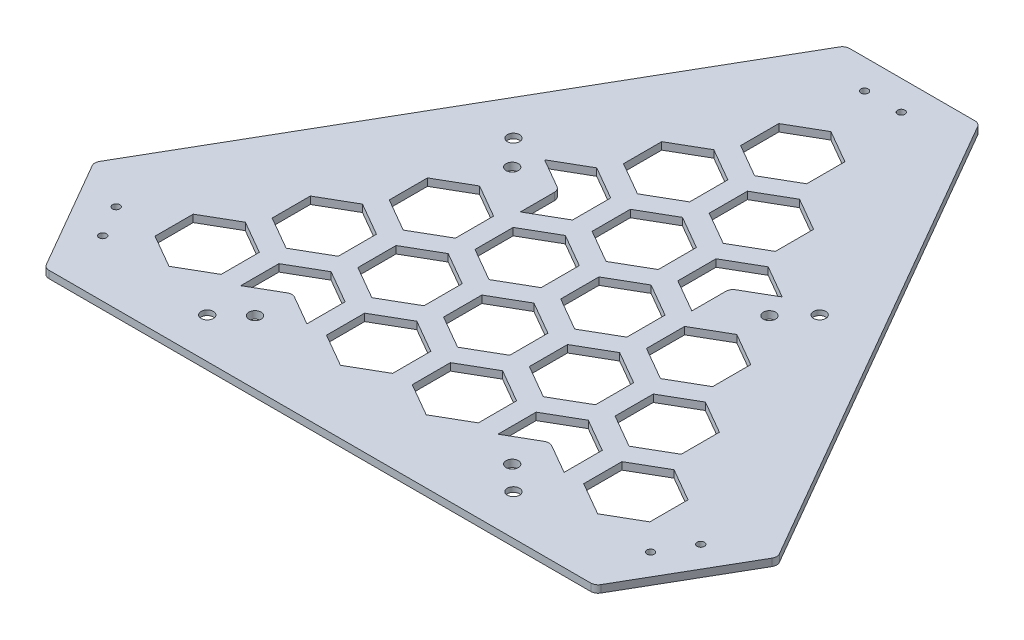
SolidWorks part; units mm, degrees
ref_plane "前基準面" through (0, 0, 0) normal (0, 0, 1) x (1, 0, 0)
ref_plane "上基準面" through (0, 0, 0) normal (0, 1, 0) x (1, 0, 0)
ref_plane "右基準面" through (0, 0, 0) normal (1, 0, 0) x (0, 0, -1)
sketch "草圖1" plane through (0, 0, 0) normal (0, 1, 0) x (1, 0, 0)
  line L0 (0, 0) -> (328.0593, 0) construction
  line L1 (139.6188, -49.0748) -> (27.3094, 145.4508)
  line L2 (-27.3094, 145.4508) -> (-139.6188, -49.0748)
  line L3 (-112.3094, -96.376) -> (112.3094, -96.376)
  line L4 (-27.3094, 145.4508) -> (27.3094, 145.4508)
  line L5 (-139.6188, -49.0748) -> (-112.3094, -96.376)
  line L6 (139.6188, -49.0748) -> (112.3094, -96.376)
  line L7 (-100, -96.376) -> (100, -96.376)
  line L8 (-100, -96.376) -> (-100, -92.376)
  line L9 (-100, -92.376) -> (100, -92.376)
  line L10 (100, -92.376) -> (100, -96.376)
  line L11 (33.4641, 134.7906) -> (133.4641, -38.4145)
  line L12 (133.4641, -38.4145) -> (130, -40.4145)
  line L13 (130, -40.4145) -> (30, 132.7906)
  line L14 (30, 132.7906) -> (33.4641, 134.7906)
  line L15 (-33.4641, 134.7906) -> (-133.4641, -38.4145)
  line L16 (-133.4641, -38.4145) -> (-130, -40.4145)
  line L17 (-130, -40.4145) -> (-30, 132.7906)
  line L18 (-30, 132.7906) -> (-33.4641, 134.7906)
  line L19 (135, -49.0748) -> (130.8333, -56.2917)
  line L20 (130, -40.4145) -> (135, -49.0748)
  line L21 (110, -92.376) -> (100, -92.376)
  line L22 (127.3692, -54.2917) -> (110.7026, -83.1592)
  line L23 (127.3692, -54.2917) -> (130.8333, -56.2917)
  line L24 (110.7026, -83.1592) -> (114.1667, -85.1592)
  line L25 (114.1667, -85.1592) -> (110, -92.376)
  line L26 (-25, 141.4508) -> (-16.6667, 141.4508)
  line L27 (-30, 132.7906) -> (-25, 141.4508)
  line L28 (25, 141.4508) -> (30, 132.7906)
  line L29 (-16.6667, 137.4508) -> (16.6667, 137.4508)
  line L30 (-16.6667, 137.4508) -> (-16.6667, 141.4508)
  line L31 (16.6667, 137.4508) -> (16.6667, 141.4508)
  line L32 (16.6667, 141.4508) -> (25, 141.4508)
  line L33 (-135, -49.0748) -> (-130.8333, -56.2917)
  line L34 (-130, -40.4145) -> (-135, -49.0748)
  line L35 (-100, -92.376) -> (-110, -92.376)
  line L36 (-127.3692, -54.2917) -> (-110.7026, -83.1592)
  line L37 (-127.3692, -54.2917) -> (-130.8333, -56.2917)
  line L38 (-110.7026, -83.1592) -> (-114.1667, -85.1592)
  line L39 (-114.1667, -85.1592) -> (-110, -92.376)
  line L40 (-16.6667, 141.4508) -> (16.6667, 141.4508)
  line L41 (-130.8333, -56.2917) -> (-114.1667, -85.1592)
  line L42 (130.8333, -56.2917) -> (114.1667, -85.1592)
  line L43 (-62.5, -79.876) -> (62.5, -79.876) construction
  line L44 (-62.5, -79.876) -> (-62.5, 45.124) construction
  circle A0 centre (0, 0) radius 96.376 construction
  point P1 (-27.3094, 145.4508)
  point P7 (27.3094, 145.4508)
  point P9 (-139.6188, -49.0748)
  point P10 (139.6188, -49.0748)
  point P11 (112.3094, -96.376)
  point P12 (-112.3094, -96.376)
  point P44 (-62.5, -79.876)
  point P47 (65.57, 71.1815)
  point P48 (119.25, -21.795)
  point P49 (62.5, -79.876)
  point P50 (62.5, 45.124)
  point P51 (-62.5, 45.124)
  point P55 (-78.5, -92.376)
  point P56 (28.86, -92.376)
  point P57 (-40.75, 114.171)
  point P58 (-94.43, 21.1945)
  dimension "D1" = 224.6188
  dimension "D2" = 54.6188
  dimension "D3" = 224.6188
  dimension "D4" = 224.6188
  dimension "D5" = 54.6188
  dimension "D6" = 54.6188
  dimension "D7" = 120
  dimension "D8" = 120
  dimension "D9" = 200
  dimension "D10" = 12.3094
  dimension "D11" = 4
  dimension "D12" = 4
  dimension "D13" = 200
  dimension "D14" = 12.3094
  dimension "D15" = 4
  dimension "D16" = 4
  dimension "D17" = 200
  dimension "D18" = 12.3094
  dimension "D19" = 4
  dimension "D20" = 50
  dimension "D21" = 4
  dimension "D22" = 4
  dimension "D23" = 33.3333
  dimension "D24" = 4
  dimension "D25" = 50
  dimension "D26" = 4
  dimension "D27" = 4
  dimension "D28" = 33.3333
  dimension "D29" = 50
  dimension "D30" = 4
  dimension "D31" = 4
  dimension "D32" = 33.3333
  dimension "D33" = 4
  dimension "D34" = 12.5
  dimension "D35" = 37.5
  dimension "D38" = 125
  dimension "D39" = 125
  dimension "D40" = 31.5
  dimension "D41" = 107.36
  dimension "D42" = 31.5
  dimension "D43" = 107.36
  dimension "D44" = 31.5
  dimension "D45" = 107.36
  dimension "D36" = 2
  dimension "D37" = 2
extrude "填料-伸長1" add sketch "草圖1" against normal blind 3 contours L38 L39 L35 L9 L21 L25 L24 L22 L23 L19 L20 L13 L28 L32 L31 L29 L30 L26 L27 L17 L34 L33 L37 L36 | L17 L18 L2 L16 | L40 L30 L29 L31 | L26 L40 L32 L28 L14 L1 L4 L2 L18 L27 | L14 L13 L12 L1 | L42 L23 L22 L24 | L19 L42 L25 L21 L10 L3 L6 L1 L12 L20 | L10 L9 L8 L3 | L41 L33 L34 L16 L2 L5 L3 L8 L35 L39 | L37 L41 L38 L36 region at (123.0127, 0, 71.0214) region at (81.7321, 0, -47.188) region at (0, 0, -142.0428) region at (0, 0, 0) region at (0, 0, 94.376) region at (-123.0127, 0, 71.0214) region at (120.7679, 0, 69.7254) region at (-81.7321, 0, -47.188) region at (0, 0, -139.4508) region at (-120.7679, 0, 69.7254)
sketch "草圖3" plane through (0, 0, 0) normal (0, 1, 0) x (1, 0, 0)
  circle A0 centre (-62.5, 45.124) radius 2.5
  circle A1 centre (62.5, 45.124) radius 2.5
  circle A2 centre (-62.5, -79.876) radius 2.5
  circle A3 centre (62.5, -79.876) radius 2.5
  dimension "D1" = 5
  dimension "D2" = 5
  dimension "D3" = 5
  dimension "D4" = 5
extrude "除料-伸長1" cut sketch "草圖3" against normal through all
sketch "草圖4" plane through (0, -3, 0) normal (0, -1, 0) x (1, 0, 0)
  circle A0 centre (-62.5, 79.876) radius 5.5
  circle A1 centre (62.5, 79.876) radius 5.5
  circle A2 centre (62.5, -45.124) radius 5.5
  circle A3 centre (-62.5, -45.124) radius 5.5
  dimension "D1" = 11
  dimension "D2" = 11
  dimension "D3" = 11
  dimension "D4" = 11
extrude "除料-伸長2" cut sketch "草圖4" against normal blind 1
sketch "草圖5" plane through (0, 0, 0) normal (0, 1, 0) x (1, 0, 0)
  line L0 (-35, -40.1769) -> (-21.5, -32.3827)
  line L1 (0, -40.1769) -> (13.5, -32.3827)
  line L2 (13.5, -32.3827) -> (13.5, -16.7942)
  line L3 (13.5, -16.7942) -> (0, -9)
  line L4 (0, -9) -> (-13.5, -16.7942)
  line L5 (-13.5, -16.7942) -> (-13.5, -32.3827)
  line L6 (-13.5, -32.3827) -> (0, -40.1769)
  line L7 (-21.5, -32.3827) -> (-21.5, -16.7942)
  line L8 (-21.5, -16.7942) -> (-35, -9)
  line L9 (-35, -9) -> (-48.5, -16.7942)
  line L10 (-48.5, -16.7942) -> (-48.5, -32.3827)
  line L11 (-48.5, -32.3827) -> (-35, -40.1769)
  line L12 (-70, -40.1769) -> (-56.5, -32.3827)
  line L13 (-56.5, -32.3827) -> (-56.5, -16.7942)
  line L14 (-56.5, -16.7942) -> (-70, -9)
  line L15 (-70, -9) -> (-83.5, -16.7942)
  line L16 (-83.5, -16.7942) -> (-83.5, -32.3827)
  line L17 (-83.5, -32.3827) -> (-70, -40.1769)
  line L24 (-17.5, -9.866) -> (-4, -2.0718)
  line L25 (-4, -2.0718) -> (-4, 13.5167)
  line L26 (-4, 13.5167) -> (-17.5, 21.3109)
  line L27 (-17.5, 21.3109) -> (-31, 13.5167)
  line L28 (-31, 13.5167) -> (-31, -2.0718)
  line L29 (-31, -2.0718) -> (-17.5, -9.866)
  line L30 (-52.5, -9.866) -> (-39, -2.0718)
  line L31 (-39, -2.0718) -> (-39, 13.5167)
  line L32 (-39, 13.5167) -> (-52.5, 21.3109)
  line L33 (-52.5, 21.3109) -> (-66, 13.5167)
  line L34 (-66, 13.5167) -> (-66, -2.0718)
  line L35 (-66, -2.0718) -> (-52.5, -9.866)
  line L42 (0, 20.4449) -> (13.5, 28.2391)
  line L43 (13.5, 28.2391) -> (13.5, 43.8275)
  line L44 (13.5, 43.8275) -> (0, 51.6218)
  line L45 (0, 51.6218) -> (-13.5, 43.8275)
  line L46 (-13.5, 43.8275) -> (-13.5, 28.2391)
  line L47 (-13.5, 28.2391) -> (0, 20.4449)
  line L48 (-35, 20.4449) -> (-21.5, 28.2391)
  line L49 (-21.5, 28.2391) -> (-21.5, 43.8275)
  line L50 (-21.5, 43.8275) -> (-35, 51.6218)
  line L51 (-35, 51.6218) -> (-48.5, 43.8275)
  line L60 (17.5, 50.7558) -> (31, 58.55)
  line L61 (31, 58.55) -> (31, 74.1384)
  line L62 (31, 74.1384) -> (17.5, 81.9327)
  line L63 (17.5, 81.9327) -> (4, 74.1384)
  line L64 (4, 74.1384) -> (4, 58.55)
  line L65 (4, 58.55) -> (17.5, 50.7558)
  line L66 (-17.5, 50.7558) -> (-4, 58.55)
  line L67 (-4, 58.55) -> (-4, 74.1384)
  line L68 (-4, 74.1384) -> (-17.5, 81.9327)
  line L69 (-17.5, 81.9327) -> (-31, 74.1384)
  line L70 (-31, 74.1384) -> (-31, 58.55)
  line L71 (-31, 58.55) -> (-17.5, 50.7558)
  line L84 (0, 81.0666) -> (13.5, 88.8609)
  line L85 (13.5, 88.8609) -> (13.5, 104.4493)
  line L86 (13.5, 104.4493) -> (0, 112.2436)
  line L87 (0, 112.2436) -> (-13.5, 104.4493)
  line L88 (-13.5, 104.4493) -> (-13.5, 88.8609)
  line L89 (-13.5, 88.8609) -> (0, 81.0666)
  line L104 (48.5, 43.8275) -> (35, 51.6218)
  line L105 (35, 51.6218) -> (21.5, 43.8275)
  line L106 (21.5, 43.8275) -> (21.5, 28.2391)
  line L107 (21.5, 28.2391) -> (35, 20.4449)
  line L120 (35, 81.0666) -> (48.5, 88.8609) [skipped]
  line L121 (48.5, 88.8609) -> (48.5, 104.4493) [skipped]
  line L122 (48.5, 104.4493) -> (35, 112.2436) [skipped]
  line L123 (35, 112.2436) -> (21.5, 104.4493) [skipped]
  line L124 (21.5, 104.4493) -> (21.5, 88.8609) [skipped]
  line L125 (21.5, 88.8609) -> (35, 81.0666) [skipped]
  line L126 (70, 81.0666) -> (83.5, 88.8609) [skipped]
  line L127 (83.5, 88.8609) -> (83.5, 104.4493) [skipped]
  line L128 (83.5, 104.4493) -> (70, 112.2436) [skipped]
  line L129 (70, 112.2436) -> (56.5, 104.4493) [skipped]
  line L130 (56.5, 104.4493) -> (56.5, 88.8609) [skipped]
  line L131 (56.5, 88.8609) -> (70, 81.0666) [skipped]
  line L132 (-35, 81.0666) -> (-21.5, 88.8609) [skipped]
  line L133 (-21.5, 88.8609) -> (-21.5, 104.4493) [skipped]
  line L134 (-21.5, 104.4493) -> (-35, 112.2436) [skipped]
  line L135 (-35, 112.2436) -> (-48.5, 104.4493) [skipped]
  line L136 (-48.5, 104.4493) -> (-48.5, 88.8609) [skipped]
  line L137 (-48.5, 88.8609) -> (-35, 81.0666) [skipped]
  line L138 (52.5, 50.7558) -> (66, 58.55) [skipped]
  line L139 (66, 58.55) -> (66, 74.1384) [skipped]
  line L140 (66, 74.1384) -> (52.5, 81.9327) [skipped]
  line L141 (52.5, 81.9327) -> (39, 74.1384) [skipped]
  line L142 (39, 74.1384) -> (39, 58.55) [skipped]
  line L143 (39, 58.55) -> (52.5, 50.7558) [skipped]
  line L144 (-52.5, 50.7558) -> (-39, 58.55) [skipped]
  line L145 (-39, 58.55) -> (-39, 74.1384) [skipped]
  line L146 (-39, 74.1384) -> (-52.5, 81.9327) [skipped]
  line L147 (-52.5, 81.9327) -> (-66, 74.1384) [skipped]
  line L148 (-66, 74.1384) -> (-66, 58.55) [skipped]
  line L149 (-66, 58.55) -> (-52.5, 50.7558) [skipped]
  line L150 (-70, 20.4449) -> (-56.5, 28.2391) [skipped]
  line L151 (-56.5, 28.2391) -> (-56.5, 43.8275) [skipped]
  line L152 (-56.5, 43.8275) -> (-70, 51.6218) [skipped]
  line L153 (-70, 51.6218) -> (-83.5, 43.8275) [skipped]
  line L154 (-83.5, 43.8275) -> (-83.5, 28.2391) [skipped]
  line L155 (-83.5, 28.2391) -> (-70, 20.4449) [skipped]
  line L156 (-87.5, -9.866) -> (-74, -2.0718) [skipped]
  line L157 (-74, -2.0718) -> (-74, 13.5167) [skipped]
  line L158 (-74, 13.5167) -> (-87.5, 21.3109) [skipped]
  line L159 (-87.5, 21.3109) -> (-101, 13.5167) [skipped]
  line L160 (-101, 13.5167) -> (-101, -2.0718) [skipped]
  line L161 (-101, -2.0718) -> (-87.5, -9.866) [skipped]
  line L162 (-105, -40.1769) -> (-91.5, -32.3827) [skipped]
  line L163 (-91.5, -32.3827) -> (-91.5, -16.7942) [skipped]
  line L164 (-91.5, -16.7942) -> (-105, -9) [skipped]
  line L165 (-105, -9) -> (-118.5, -16.7942) [skipped]
  line L166 (-118.5, -16.7942) -> (-118.5, -32.3827) [skipped]
  line L167 (-118.5, -32.3827) -> (-105, -40.1769) [skipped]
  line L180 (52.5, -9.866) -> (66, -2.0718)
  line L181 (66, -2.0718) -> (66, 13.5167)
  line L182 (66, 13.5167) -> (52.5, 21.3109)
  line L183 (52.5, 21.3109) -> (39, 13.5167)
  line L184 (39, 13.5167) -> (39, -2.0718)
  line L185 (39, -2.0718) -> (52.5, -9.866)
  line L192 (17.5, -9.866) -> (31, -2.0718)
  line L193 (31, -2.0718) -> (31, 13.5167)
  line L194 (31, 13.5167) -> (17.5, 21.3109)
  line L195 (17.5, 21.3109) -> (4, 13.5167)
  line L196 (4, 13.5167) -> (4, -2.0718)
  line L197 (4, -2.0718) -> (17.5, -9.866)
  line L198 (17.5, -9.866) -> (31, -2.0718) [skipped]
  line L199 (31, -2.0718) -> (31, 13.5167) [skipped]
  line L200 (31, 13.5167) -> (17.5, 21.3109) [skipped]
  line L201 (17.5, 21.3109) -> (4, 13.5167) [skipped]
  line L202 (4, 13.5167) -> (4, -2.0718) [skipped]
  line L203 (4, -2.0718) -> (17.5, -9.866) [skipped]
  line L204 (87.5, -9.866) -> (101, -2.0718) [skipped]
  line L205 (101, -2.0718) -> (101, 13.5167) [skipped]
  line L206 (101, 13.5167) -> (87.5, 21.3109) [skipped]
  line L207 (87.5, 21.3109) -> (74, 13.5167) [skipped]
  line L208 (74, 13.5167) -> (74, -2.0718) [skipped]
  line L209 (74, -2.0718) -> (87.5, -9.866) [skipped]
  line L210 (35, -40.1769) -> (48.5, -32.3827)
  line L211 (48.5, -32.3827) -> (48.5, -16.7942)
  line L212 (48.5, -16.7942) -> (35, -9)
  line L213 (35, -9) -> (21.5, -16.7942)
  line L214 (21.5, -16.7942) -> (21.5, -32.3827)
  line L215 (21.5, -32.3827) -> (35, -40.1769)
  line L216 (70, -40.1769) -> (83.5, -32.3827)
  line L217 (83.5, -32.3827) -> (83.5, -16.7942)
  line L218 (83.5, -16.7942) -> (70, -9)
  line L219 (70, -9) -> (56.5, -16.7942)
  line L220 (56.5, -16.7942) -> (56.5, -32.3827)
  line L221 (56.5, -32.3827) -> (70, -40.1769)
  line L228 (17.5, -70.4878) -> (31, -62.6936)
  line L229 (31, -62.6936) -> (31, -47.1051)
  line L230 (31, -47.1051) -> (17.5, -39.3109)
  line L231 (17.5, -39.3109) -> (4, -47.1051)
  line L232 (4, -47.1051) -> (4, -62.6936)
  line L233 (4, -62.6936) -> (17.5, -70.4878)
  line L235 (66, -62.6936) -> (66, -47.1051)
  line L236 (66, -47.1051) -> (52.5, -39.3109)
  line L237 (52.5, -39.3109) -> (39, -47.1051)
  line L238 (39, -47.1051) -> (39, -62.6936)
  line L240 (87.5, -70.4878) -> (101, -62.6936)
  line L241 (101, -62.6936) -> (101, -47.1051)
  line L242 (101, -47.1051) -> (87.5, -39.3109)
  line L243 (87.5, -39.3109) -> (74, -47.1051)
  line L244 (74, -47.1051) -> (74, -62.6936)
  line L245 (74, -62.6936) -> (87.5, -70.4878)
  line L246 (-17.5, -70.4878) -> (-4, -62.6936)
  line L247 (-4, -62.6936) -> (-4, -47.1051)
  line L248 (-4, -47.1051) -> (-17.5, -39.3109)
  line L249 (-17.5, -39.3109) -> (-31, -47.1051)
  line L250 (-31, -47.1051) -> (-31, -62.6936)
  line L251 (-31, -62.6936) -> (-17.5, -70.4878)
  line L252 (35, -40.1769) -> (48.5, -32.3827) [skipped]
  line L253 (48.5, -32.3827) -> (48.5, -16.7942) [skipped]
  line L254 (48.5, -16.7942) -> (35, -9) [skipped]
  line L255 (35, -9) -> (21.5, -16.7942) [skipped]
  line L256 (21.5, -16.7942) -> (21.5, -32.3827) [skipped]
  line L257 (21.5, -32.3827) -> (35, -40.1769) [skipped]
  line L258 (70, -40.1769) -> (83.5, -32.3827) [skipped]
  line L259 (83.5, -32.3827) -> (83.5, -16.7942) [skipped]
  line L260 (83.5, -16.7942) -> (70, -9) [skipped]
  line L261 (70, -9) -> (56.5, -16.7942) [skipped]
  line L262 (56.5, -16.7942) -> (56.5, -32.3827) [skipped]
  line L263 (56.5, -32.3827) -> (70, -40.1769) [skipped]
  line L264 (105, -40.1769) -> (118.5, -32.3827) [skipped]
  line L265 (118.5, -32.3827) -> (118.5, -16.7942) [skipped]
  line L266 (118.5, -16.7942) -> (105, -9) [skipped]
  line L267 (105, -9) -> (91.5, -16.7942) [skipped]
  line L268 (91.5, -16.7942) -> (91.5, -32.3827) [skipped]
  line L269 (91.5, -32.3827) -> (105, -40.1769) [skipped]
  line L271 (-39, -62.6936) -> (-39, -47.1051)
  line L272 (-39, -47.1051) -> (-52.5, -39.3109)
  line L273 (-52.5, -39.3109) -> (-66, -47.1051)
  line L274 (-66, -47.1051) -> (-66, -62.6936)
  line L276 (-87.5, -70.4878) -> (-74, -62.6936)
  line L277 (-74, -62.6936) -> (-74, -47.1051)
  line L278 (-74, -47.1051) -> (-87.5, -39.3109)
  line L279 (-87.5, -39.3109) -> (-101, -47.1051)
  line L280 (-101, -47.1051) -> (-101, -62.6936)
  line L281 (-101, -62.6936) -> (-87.5, -70.4878)
  line L282 (-66, -62.6936) -> (-52.5, -54.8993)
  line L283 (-52.5, -54.8993) -> (-39, -62.6936)
  line L284 (52.5, -54.8993) -> (39, -62.6936)
  line L285 (52.5, -54.8993) -> (66, -62.6936)
  line L286 (-48.5, 43.8275) -> (-35, 36.0333)
  line L287 (-35, 36.0333) -> (-35, 20.4449)
  line L288 (35, 36.0333) -> (35, 20.4449)
  line L289 (35, 36.0333) -> (48.5, 43.8275)
  line L291 (-52.5, -70.4878) -> (-39, -62.6936) [skipped]
  line L292 (-66, -62.6936) -> (-52.5, -70.4878) [skipped]
  line L293 (39, -62.6936) -> (52.5, -70.4878) [skipped]
  line L294 (52.5, -70.4878) -> (66, -62.6936) [skipped]
  line L295 (48.5, 28.2391) -> (48.5, 43.8275) [skipped]
  line L296 (35, 20.4449) -> (48.5, 28.2391) [skipped]
  line L297 (-48.5, 43.8275) -> (-48.5, 28.2391) [skipped]
  line L298 (-48.5, 28.2391) -> (-35, 20.4449) [skipped]
  circle A0 centre (0, -24.5885) radius 13.5 construction
  dimension "D1" = 27
  dimension "D2" = 9
  dimension "D3" = 4
  dimension "D4" = 5
  dimension "D5" = 3
  dimension "D6" = 2
  dimension "D7" = 4
  dimension "D8" = 2
  dimension "D9" = 3
extrude "除料-伸長3" cut sketch "草圖5" against normal through all
sketch "草圖7" plane through (0, -3, 0) normal (0, -1, 0) x (1, 0, 0)
  line L0 (-25, -142.4508) -> (25, -142.4508)
  line L1 (118.4558, 59.7302) -> (132.1132, 36.0748) construction
  line L2 (110.9558, 72.7206) -> (97.2983, 96.376) construction
  line L3 (-27.3094, -145.4508) -> (27.3094, -145.4508) construction
  line L4 (-7.5, -132.4508) -> (-30.1962, -132.4508) construction
  line L5 (-130, 40.4145) -> (-30, -132.7906) construction
  line L6 (7.5, -132.4508) -> (30.1962, -132.4508) construction
  line L7 (130, 40.4145) -> (30, -132.7906) construction
  line L8 (137.8868, 46.0748) -> (108.8453, 96.376)
  line L9 (139.6188, 49.0748) -> (112.3094, 96.376) construction
  line L10 (139.6188, 49.0748) -> (27.3094, -145.4508) construction
  line L11 (-112.3094, 96.376) -> (112.3094, 96.376) construction
  line L12 (118.4558, 59.7302) -> (127.116, 64.7302) construction
  line L13 (110.9558, 72.7206) -> (119.616, 77.7206) construction
  line L14 (-137.8868, 46.0748) -> (-108.8453, 96.376)
  line L15 (-27.3094, -145.4508) -> (-139.6188, 49.0748) construction
  line L16 (-139.6188, 49.0748) -> (-112.3094, 96.376) construction
  line L17 (-118.4558, 59.7302) -> (-127.116, 64.7302) construction
  line L18 (-110.9558, 72.7206) -> (-119.616, 77.7206) construction
  line L19 (-110.9558, 72.7206) -> (-97.2983, 96.376) construction
  line L20 (-118.4558, 59.7302) -> (-132.1132, 36.0748) construction
  point P2 (7.5, -132.4508)
  point P5 (-7.5, -132.4508)
  point P20 (118.4558, 59.7302)
  point P33 (-118.4558, 59.7302)
  point P34 (-110.9558, 72.7206)
  point P39 (-7.5, -133.4508)
  point P42 (7.5, -133.4508)
  point P43 (119.3218, 60.2302)
  point P44 (-111.8218, 73.2206)
  point P45 (111.8218, 73.2206)
  point P46 (-119.3218, 60.2302)
  point P52 (110.9558, 72.7206)
  dimension "D1" = 3
  dimension "D2" = 15
  dimension "D3" = 10
  dimension "D4" = 3
  dimension "D5" = 10
  dimension "D6" = 10
  dimension "D7" = 15
  dimension "D8" = 3
  dimension "D9" = 10
  dimension "D10" = 10
  dimension "D11" = 15
  dimension "D12" = 1
  dimension "D13" = 1
  dimension "D14" = 1
  dimension "D15" = 1
  dimension "D16" = 1
  dimension "D17" = 1
hole_wizard "Ø3.0mm 定位孔1" positions "3D草圖4" profile "草圖12" hole size "Ø3.0" standard "GB" end condition through all
sketch3d "3D草圖4"
  point P0 (111.8218, -3, 73.2206)
  point P3 (119.3218, -3, 60.2302)
  point P6 (7.5, -3, -133.4508)
  point P9 (-7.5, -3, -133.4508)
  point P12 (-111.8218, -3, 73.2206)
  point P15 (-119.3218, -3, 60.2302)
sketch "草圖12" plane through (111.8218, -3, 73.2206) normal (1, 0, 0) x (0, 0, -1)
  line L0 (0, 0) -> (0, 3)
  line L1 (0, 3) -> (1.5, 3)
  line L2 (1.5, 3) -> (1.5, 0)
  line L5 (1.5, 0) -> (0, 0)
  line L11 (0, -6.35) -> (0, 107.95) construction
  dimension "貫穿孔直徑" = 3
  dimension "貫穿孔深度" = 3
fillet "圓角1" radius 3 10 edges at (139.6188, -1.5, 49.0748) (112.3094, -1.5, 96.376) (-112.3094, -1.5, 96.376) (-139.6188, -1.5, 49.0748) (-27.3094, -1.5, -145.4508) (27.3094, -1.5, -145.4508) (-52.5, -1.5, 54.8993) (52.5, -1.5, 54.8993) (35, -1.5, -36.0333) (-35, -1.5, -36.0333)
sketch "草圖9" plane through (0, 0, 0) normal (0, 1, 0) x (1, 0, 0)
  line L0 (-52.5, -70.376) -> (52.5, -70.376) construction
  line L1 (-52.5, -70.376) -> (-52.5, 34.624) construction
  line L2 (-110.5774, -96.376) -> (110.5774, -96.376) construction
  point P0 (-52.5, -70.376)
  point P3 (52.5, -70.376)
  point P4 (52.5, 34.624)
  point P5 (-52.5, 34.624)
  dimension "D3" = 105
  dimension "D4" = 105
  dimension "D5" = 26
  dimension "D1" = 2
  dimension "D2" = 2
hole_wizard "Ø5.0mm 定位孔1" positions "3D草圖2" profile "草圖10" hole size "Ø5.0" standard "GB" end condition through all
sketch3d "3D草圖2"
  point P0 (-52.5, 0, -34.624)
  point P3 (52.5, 0, -34.624)
  point P6 (52.5, 0, 70.376)
  point P9 (-52.5, 0, 70.376)
sketch "草圖10" plane through (-52.5, 0, -34.624) normal (1, 0, 0) x (0, 0, 1)
  line L0 (0, 0) -> (0, 3)
  line L1 (0, 3) -> (2.5, 3)
  line L2 (2.5, 3) -> (2.5, 0)
  line L5 (2.5, 0) -> (0, 0)
  line L11 (0, -6.35) -> (0, 107.95) construction
  dimension "貫穿孔直徑" = 5
  dimension "貫穿孔深度" = 3
